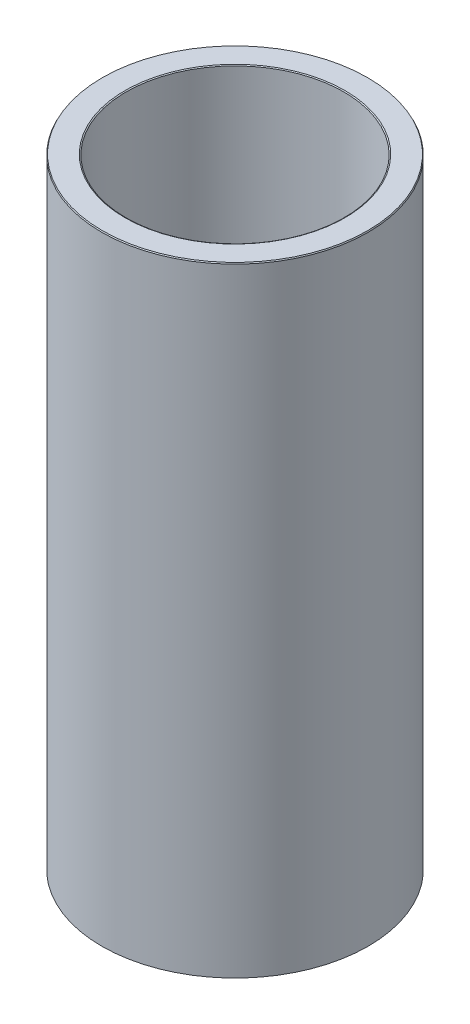
SolidWorks part; units mm, degrees
ref_plane "Front Plane" through (0, 0, 0) normal (0, 0, 1) x (1, 0, 0)
ref_plane "Top Plane" through (0, 0, 0) normal (0, 1, 0) x (1, 0, 0)
ref_plane "Right Plane" through (0, 0, 0) normal (1, 0, 0) x (0, 0, -1)
sketch "Sketch1" plane through (0, 0, 0) normal (0, 1, 0) x (1, 0, 0)
  circle A0 centre (0, 0) radius 35
  dimension "SLEEVE_OD" = 70
extrude "Boss-Extrude1" add sketch "Sketch1" along normal blind 162.8812
sketch "Sketch2" plane through (0, 0, 0) normal (0, 1, 0) x (1, 0, 0)
  circle A0 centre (0, 0) radius 28.6381
  dimension "BORE_D" = 57.2763
extrude "Cut-Extrude1" cut sketch "Sketch2" along normal through all
chamfer "Chamfer1" distance 0.2875 angle 30.256 4 edges at (0, 162.8812, 28.6381) (0, 0, 28.6381) (0, 0, 35) (0, 162.8812, 35) first distance on face at (0, 162.8812, 28.6381) first distance on face at (0, 0, 28.6381) first distance on face at (0, 162.8812, 35)
